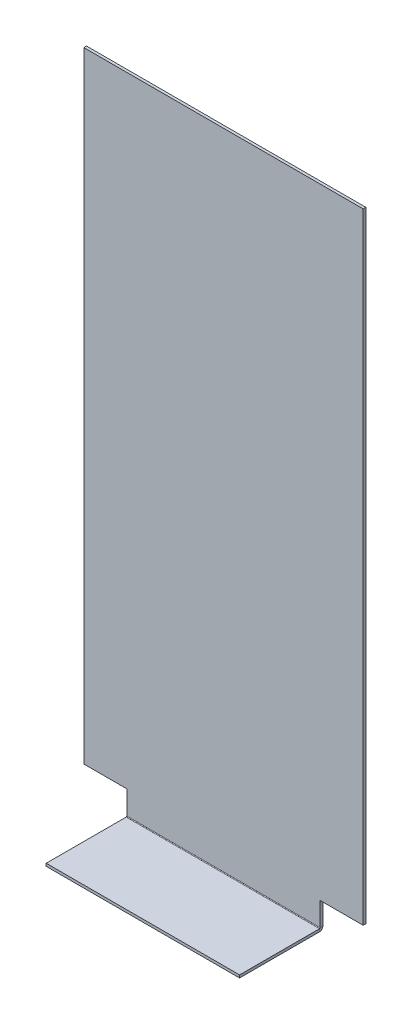
SolidWorks part; units mm, degrees
note: The reader was unsure of these and kept them because the rebuilt part matched: bend radius of "BaseBend1".
material "ABS PC"
ref_plane "Front" through (0, 0, 0) normal (0, 0, 1) x (1, 0, 0)
ref_plane "Top" through (0, 0, 0) normal (0, 1, 0) x (1, 0, 0)
ref_plane "Right" through (0, 0, 0) normal (1, 0, 0) x (0, 0, -1)
sketch "Sketch1" plane through (0, 0, 0) normal (1, 0, 0) x (0, 0, -1)
  line L0 (-95.25, 0) -> (0, 0)
  line L1 (0, 0) -> (0, 762)
  dimension "D1" = 95.25
  dimension "D2" = 762
base flange "Base-Flange1" sketch "Sketch1" end condition mid plane depth 228.6 reverse direction no thickness 3.175 reverse thickness direction no bend radius 0.7366
bend "BaseBend1" bend radius 0.7366 bend angle 90 parameters "D5"=1
sketch "Sketch6" plane through (0, 0, -3.175) normal (0, 0, -1) x (-1, 0, 0)
  line L0 (-114.3, -3.175) -> (114.3, -3.175) construction
  line L1 (-114.3, 762) -> (-165.1, 762)
  line L2 (-114.3, 762) -> (-114.3, 28.575)
  line L3 (-114.3, 28.575) -> (-165.1, 28.575)
  line L4 (-165.1, 762) -> (-165.1, 28.575)
  line L5 (114.3, 762) -> (165.1, 762)
  line L6 (114.3, 762) -> (114.3, 28.575)
  line L7 (114.3, 28.575) -> (165.1, 28.575)
  line L8 (165.1, 762) -> (165.1, 28.575)
  dimension "D1" = 330.2
  dimension "D2" = 31.75
base flange "Tab1" sketch "Sketch6" thickness 3.175 reverse thickness direction no parameters "D1"=0.7366
sketch "Bend-Lines1" plane through (0, 0, 0) normal (0, 1, 0) x (1, 0, 0)
sketch "Bounding-Box1" plane through (0, 0, 0) normal (0, 1, 0) x (1, 0, 0)
sheet metal parameters "Sheet-Metal8" thickness 3.175 parameters "D1"=0.7366
flat pattern "Flat-Pattern8" [suppressed]
sketch "Bend-Lines2" plane through (0, 0, 0) normal (0, 1, 0) x (1, 0, 0)
sketch "Bounding-Box2" [suppressed] plane through (0, 0, 0) normal (0, 1, 0) x (1, 0, 0)
bend of the flat pattern "Flatten-<BaseBend1>1"
sheet metal parameters "Sheet-Metal9" thickness 3.175 parameters "D1"=0.7366
flat pattern "Flat-Pattern9" [suppressed]
sketch "Bend-Lines3" plane through (0, 0, 0) normal (0, 1, 0) x (1, 0, 0)
sketch "Bounding-Box3" [suppressed] plane through (0, 0, 0) normal (0, 1, 0) x (1, 0, 0)
bend of the flat pattern "Flatten-<BaseBend1>2"
